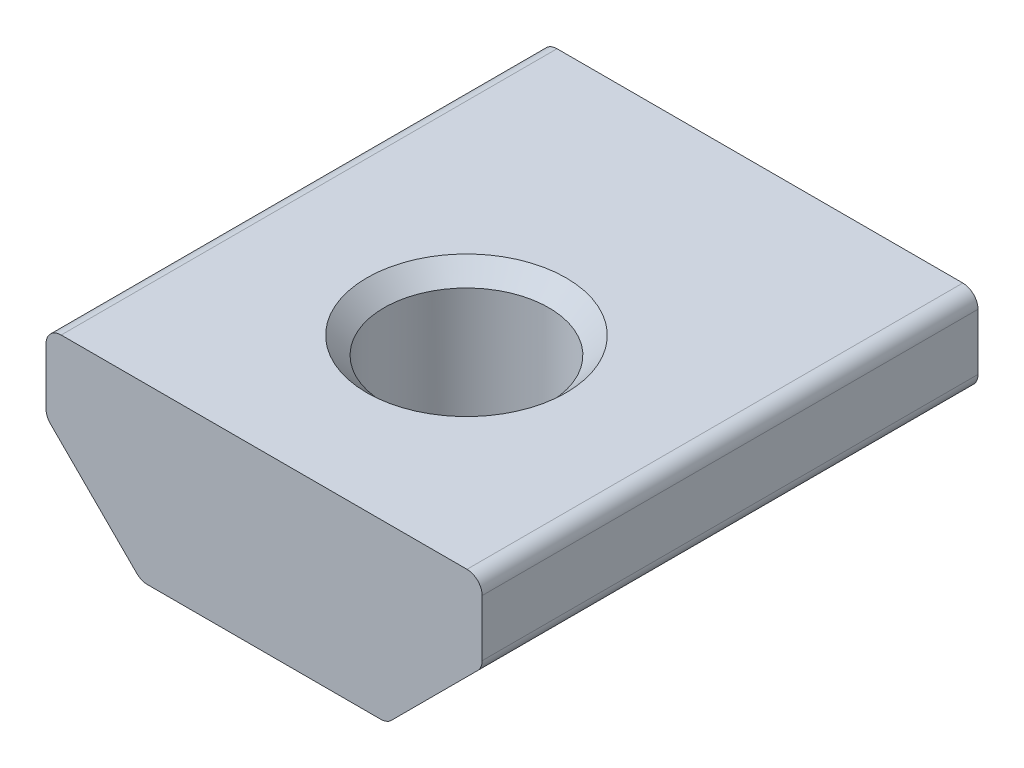
SolidWorks part; units mm, degrees
ref_plane "Front Plane" through (0, 0, 0) normal (0, 0, 1) x (1, 0, 0)
ref_plane "Top Plane" through (0, 0, 0) normal (0, 1, 0) x (1, 0, 0)
ref_plane "Right Plane" through (0, 0, 0) normal (1, 0, 0) x (0, 0, -1)
ref_plane "Plane1" through (0, 0, 5.08) normal (0, 0, 1) x (1, 0, 0)
sketch "Sketch1" plane through (0, 0, 5.08) normal (0, 0, 1) x (1, 0, 0)
  line L0 (5.4737, 4.3434) -> (-5.4737, 4.3434)
  line L1 (-5.4737, 4.3434) -> (-5.4737, 2.3889)
  line L2 (-5.4737, 2.3889) -> (-3.0848, 0)
  line L3 (-3.0848, 0) -> (3.0848, 0)
  line L4 (3.0848, 0) -> (5.4737, 2.3889)
  line L5 (5.4737, 2.3889) -> (5.4737, 4.3434)
extrude "Boss-Extrude1" add sketch "Sketch1" against normal blind 12.446
hole_wizard "#6 Clearance Hole1" positions "Sketch3" profile "Sketch2" hole size "#6" standard "ANSI Inch"
sketch "Sketch3" plane through (0, 4.3434, 0) normal (0, 1, 0) x (1, 0, 0)
  point P0 (0, 0)
sketch "Sketch2" plane through (0, 4.3434, 0) normal (1, 0, 0) x (0, 0, 1)
  line L0 (0, 0) -> (0, 4.3434)
  line L1 (0, 4.3434) -> (2.067, 4.3434)
  line L2 (2.067, 4.3434) -> (2.067, 0)
  line L5 (2.067, 0) -> (0, 0)
  line L11 (0, -6.35) -> (0, 107.95) construction
  dimension "Thru Hole Dia." = 4.134
  dimension "Thru Hole Depth" = 4.3434
chamfer "Chamfer1" distance 0.433 angle 45 2 edges at (0, 0, 2.067) (0, 4.3434, 2.067)
fillet "Fillet1" radius 0.381 6 edges at (-3.0848, 0, -1.143) (-5.4737, 4.3434, -1.143) (-5.4737, 2.3889, -1.143) (5.4737, 4.3434, -1.143) (3.0848, 0, -1.143) (5.4737, 2.3889, -1.143) tangent propagation no
